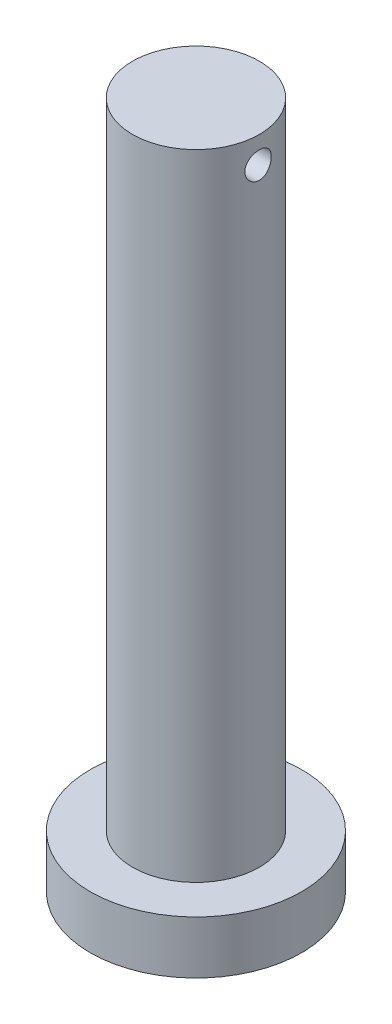
SolidWorks part; units mm, degrees
ref_plane "Front Plane" through (0, 0, 0) normal (0, 0, 1) x (1, 0, 0)
ref_plane "Top Plane" through (0, 0, 0) normal (0, 1, 0) x (1, 0, 0)
ref_plane "Right Plane" through (0, 0, 0) normal (1, 0, 0) x (0, 0, -1)
sketch "Sketch1" plane through (0, 0, 0) normal (0, 1, 0) x (1, 0, 0)
  circle A0 centre (0, 0) radius 6
  circle A1 centre (0, 0) radius 10
  dimension "D1" = 12
  dimension "D2" = 20
extrude "Boss-Extrude1" add sketch "Sketch1" along normal blind 60 contours A0
extrude "Boss-Extrude2" add sketch "Sketch1<3>" against normal blind 5 contours A1
sketch "Sketch1<3>" plane through (0, 0, 0) normal (0, 1, 0) x (1, 0, 0) same geometry as "Sketch1"
sketch "Sketch2" plane through (0, 0, 0) normal (1, 0, 0) x (0, 0, -1)
  line L0 (6, 60) -> (-6, 60) construction
  line L1 (6, 0) -> (6, 60) construction
  circle A0 centre (0, 57.5) radius 1.25
  point P6 (5.8741, 55.4511)
  dimension "D1" = 2.5
  dimension "D2" = 2.5
  dimension "D3" = 6
extrude "Cut-Extrude1" cut sketch "Sketch2" against normal through all both and the other way through all
